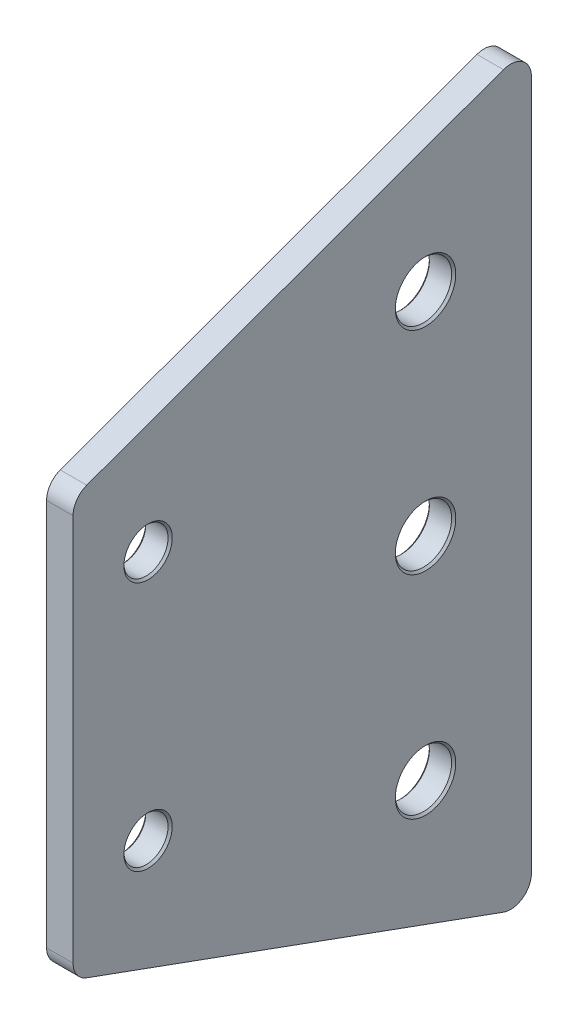
SolidWorks part; units mm, degrees
material "6061 Alloy"
ref_plane "Front Plane" through (0, 0, 0) normal (0, 0, 1) x (1, 0, 0)
ref_plane "Top Plane" through (0, 0, 0) normal (0, 1, 0) x (1, 0, 0)
ref_plane "Right Plane" through (0, 0, 0) normal (1, 0, 0) x (0, 0, -1)
sketch "Sketch1" plane through (0, 0, 0) normal (1, 0, 0) x (0, 0, -1)
  line L0 (-27.5, 0) -> (27.5, 0) construction
  line L1 (-27.5, 25) -> (-27.5, -25)
  line L3 (27.5, 45) -> (27.5, -45)
  line L4 (-27.5, 25) -> (27.5, 45)
  line L5 (-27.5, -25) -> (27.5, -45)
  dimension "D1" = 50
  dimension "D4" = 55
  dimension "D5" = 90
extrude "1/8 Inch Sheet" add sketch "Sketch1" along normal mid plane 3.175
hole_wizard "M5 Clearance Hole1" positions "Sketch5" profile "Sketch6" hole size "M5" standard "ANSI Metric" end condition up to next
sketch "Sketch5" plane through (1.5875, 0, 0) normal (1, 0, 0) x (0, 0, -1)
  line L0 (0, 0) -> (-27.5, 0) construction
  line L1 (-27.5, 25) -> (-27.5, -25) construction
  line L3 (-18.5, 15) -> (-18.5, 0) construction
  line L5 (-18.5, 0) -> (-18.5, -15) construction
  point P0 (-18.5, 15)
  point P2 (-18.5, -15)
  dimension "D1" = 9
  dimension "D2" = 15
sketch "Sketch6" plane through (1.5875, 15, 18.5) normal (0, 1, 0) x (0, 0, -1)
  line L0 (0, 0) -> (0, 3.175)
  line L1 (0, 3.175) -> (2.65, 3.175)
  line L2 (2.65, 3.175) -> (2.65, 0)
  line L5 (2.65, 0) -> (0, 0)
  line L11 (0, -6.35) -> (0, 107.95) construction
  dimension "Thru Hole Dia." = 5.3
  dimension "Thru Hole Depth" = 3.175
hole_wizard "1/4 in Clearance Hole1" positions "Sketch3" profile "Sketch4" hole size "1/4" standard "ANSI Inch" end condition up to next
sketch "Sketch3" plane through (1.5875, 0, 0) normal (1, 0, 0) x (0, 0, -1)
  line L0 (0, 0) -> (14.8, 0) construction
  line L1 (14.8, 0) -> (14.8, 25.4) construction
  line L2 (14.8, 0) -> (14.8, -25.4) construction
  line L5 (27.5, -45) -> (27.5, 45) construction
  point P0 (14.8, 25.4)
  point P2 (14.8, 0)
  point P4 (14.8, -25.4)
  dimension "D2" = 25.4
  dimension "D1" = 12.7
sketch "Sketch4" plane through (1.5875, 25.4, -14.8) normal (0, 1, 0) x (0, 0, -1)
  line L0 (0, 0) -> (0, 3.175)
  line L1 (0, 3.175) -> (3.3782, 3.175)
  line L2 (3.3782, 3.175) -> (3.3782, 0)
  line L5 (3.3782, 0) -> (0, 0)
  line L11 (0, -6.35) -> (0, 107.95) construction
  dimension "Thru Hole Dia." = 6.7564
  dimension "Thru Hole Depth" = 3.175
chamfer "Chamfer 0.5 mm" distance 0.25 angle 45 10 edges at (-1.5875, 25.4, -11.4218) (1.5875, 25.4, -18.1782) (-1.5875, 0, -11.4218) (1.5875, 0, -18.1782) (-1.5875, -25.4, -11.4218) (1.5875, -25.4, -18.1782) (-1.5875, -15, 21.15) (1.5875, -15, 15.85) (-1.5875, 15, 21.15) (1.5875, 15, 15.85)
fillet "Fillet1" radius 2.5 4 edges at (0, 45, -27.5) (0, -45, -27.5) (0, -25, 27.5) (0, 25, 27.5)
equation "\"D1@Sketch3\"= 25.4/2"
